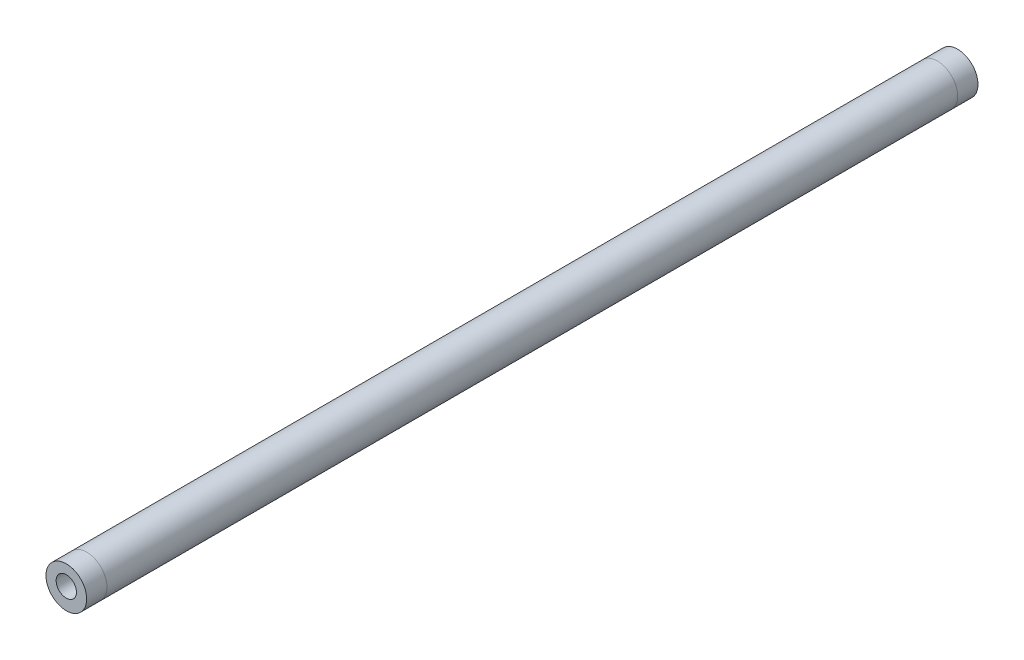
SolidWorks part; units mm, degrees
material "AISI 4130 Steel, normalized at 870C"
ref_plane "Front Plane" through (0, 0, 0) normal (0, 0, 1) x (1, 0, 0)
ref_plane "Top Plane" through (0, 0, 0) normal (0, 1, 0) x (1, 0, 0)
ref_plane "Right Plane" through (0, 0, 0) normal (1, 0, 0) x (0, 0, -1)
sketch "Axis" plane through (0, 0, 0) normal (0, 1, 0) x (1, 0, 0)
  line L0 (0, 0) -> (0, 21.9075) construction
  line L1 (0, 21.9075) -> (0, 300.0818) construction
  line L2 (0, 300.0818) -> (0, 321.9893) construction
  dimension "D1" = 21.9075
  dimension "D2" = 321.9893
sketch "Sketch2" plane through (0, 0, 0) normal (0, 0, 1) x (1, 0, 0)
  circle A0 centre (0, 0) radius 6.35
  circle A1 centre (0, 0.235) radius 3.175
  circle A2 centre (0, 0) radius 4.7625
  dimension "D1" = 12.7
  dimension "D2" = 6.35
  dimension "D3" = 9.525
extrude "Threaded Insert 1-1" add sketch "Sketch2" against normal blind 6.35 from vertex contours A0 A2 | A2 A1 region at (-6.1704, 0, 0) region at (-4.6278, 0, 0) starting at point (0, 0, -21.9075)
extrude "Threaded Insert 1-2" add sketch "Sketch2<5>" against normal blind 9.525 from surface contours A2 A1 region at (-4.6278, 0, 0) starting at face at (6.35, 0, -28.2575)
sketch "Sketch2<5>" plane through (0, 0, 0) normal (0, 0, 1) x (1, 0, 0) same geometry as "Sketch2"
extrude "Boss-Extrude4" add sketch "Sketch2<7>" along normal blind 6.35 from vertex separate body contours A0 A2 | A2 A1 region at (-6.1704, 0, 0) region at (-4.6278, 0, 0) starting at point (0, 0, -300.0818)
sketch "Sketch2<7>" plane through (0, 0, 0) normal (0, 0, 1) x (1, 0, 0) same geometry as "Sketch2"
extrude "Boss-Extrude5" add sketch "Sketch2<8>" along normal blind 9.525 from surface contours A2 A1 region at (-4.6278, 0, 0) starting at face at (6.35, 0, -293.7318)
sketch "Sketch2<8>" plane through (0, 0, 0) normal (0, 0, 1) x (1, 0, 0) same geometry as "Sketch2"
extrude "Boss-Extrude6" add sketch "Sketch2<9>" against normal up to surface (293.7318 mm away) from surface separate body contours A0 A2 region at (-6.1704, 0, 0) up to face at (6.35, 0, -293.7318) starting at face at (4.7625, 0, -28.2575)
sketch "Sketch2<9>" plane through (0, 0, 0) normal (0, 0, 1) x (1, 0, 0) same geometry as "Sketch2"
equation "\"Tube Outer Diameter\"= .5"
equation "\"Tube Inner Diameter\"= .375"
equation "\"Rod end Diameter\"= .25"
equation "\"Threaded Insert Out\"= .25"
equation "\"Threaded Insert In\"= .375'`"
equation "\"D1@Sketch2\"=\"Tube Outer Diameter\""
equation "\"D2@Sketch2\"=\"Rod end Diameter\""
equation "\"D1@Threaded Insert 1-1\" = \"Threaded Insert Out\""
equation "\"D3@Sketch2\"=\"Tube Inner Diameter\""
equation "\"D1@Threaded Insert 1-2\" = \"Threaded Insert In\""
equation "\"D1@Boss-Extrude4\"=\"Threaded Insert Out\""
equation "\"D1@Boss-Extrude5\"=\"Threaded Insert In\""
